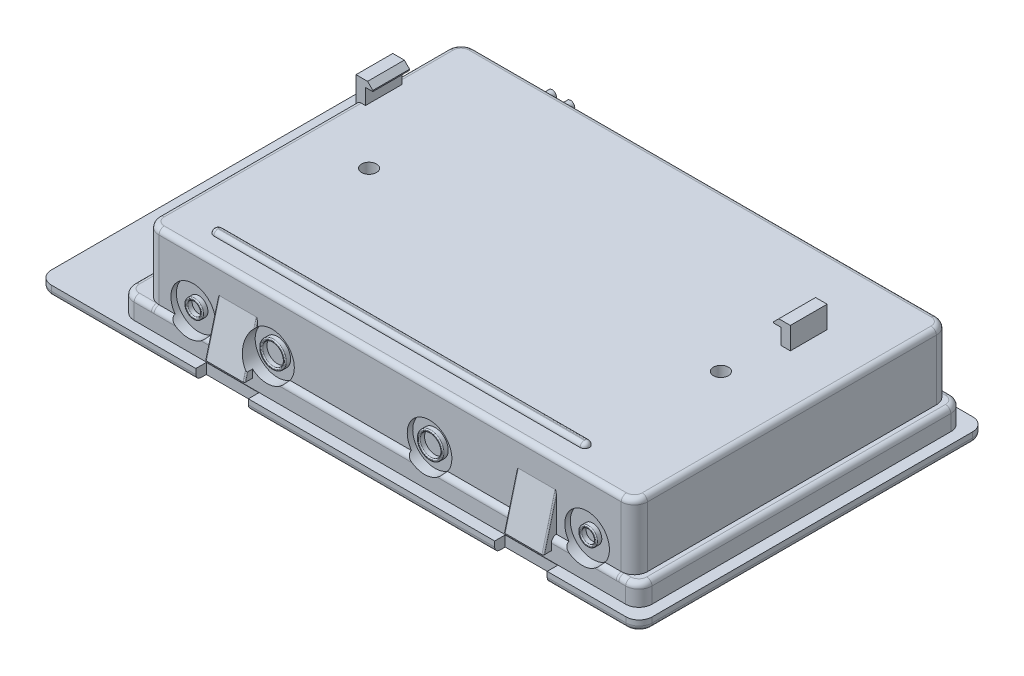
SolidWorks part; units mm, degrees
ref_plane "Front Plane" through (0, 0, 0) normal (0, 0, 1) x (1, 0, 0)
ref_plane "Top Plane" through (0, 0, 0) normal (0, 1, 0) x (1, 0, 0)
ref_plane "Right Plane" through (0, 0, 0) normal (1, 0, 0) x (0, 0, -1)
sketch "Sketch1" plane through (0, 0, 0) normal (0, 1, 0) x (1, 0, 0)
  line L0 (-21.0657, 0) -> (0, 0) construction
  line L1 (0, 0) -> (0, 20.0058) construction
  line L3 (-57.2, 33) -> (57.2, 33)
  line L4 (-57.2, 33) -> (-57.2, -33)
  line L5 (-57.2, -33) -> (57.2, -33)
  line L6 (57.2, 33) -> (57.2, -33)
  dimension "D1" = 114.4
  dimension "D2" = 66
extrude "Boss-Extrude1" add sketch "Sketch1" along normal blind 2
sketch "Sketch2" plane through (0, 2, 0) normal (0, 1, 0) x (1, 0, 0)
  line L0 (0, 0) -> (18.8821, 0) construction
  line L1 (-43.5, 30.95) -> (55.1, 30.95)
  line L2 (-43.5, 30.95) -> (-43.5, -30.95)
  line L3 (-43.5, -30.95) -> (55.1, -30.95)
  line L4 (55.1, 30.95) -> (55.1, -30.95)
  line L5 (57.2, -33) -> (57.2, 33) construction
  dimension "D1" = 98.6
  dimension "D2" = 61.9
  dimension "D3" = 2.1
extrude "Boss-Extrude2" add sketch "Sketch2" along normal blind 4
sketch "Sketch3" plane through (0, 6, 0) normal (0, 1, 0) x (1, 0, 0)
  line L0 (0, 0) -> (11.2165, 0) construction
  line L1 (55.1, -30.95) -> (55.1, 30.95) construction
  line L2 (-39.7, 30) -> (53.3, 30)
  line L3 (-39.7, 30) -> (-39.7, -30)
  line L4 (-39.7, -30) -> (53.3, -30)
  line L5 (53.3, 30) -> (53.3, -30)
  dimension "D1" = 60
  dimension "D2" = 93
  dimension "D3" = 1.8
extrude "Boss-Extrude3" add sketch "Sketch3" along normal blind 12.5
fillet "Fillet1" radius 2.5 12 edges at (-57.2, 1, -33) (-43.5, 4, -30.95) (57.2, 1, -33) (55.1, 4, -30.95) (57.2, 1, 33) (55.1, 4, 30.95) (-57.2, 1, 33) (-43.5, 4, 30.95) (53.3, 12.25, 30) (-39.7, 12.25, 30) (-39.7, 12.25, -30) (53.3, 12.25, -30)
sketch "Sketch4" plane through (0, 18.5, 0) normal (0, 1, 0) x (1, 0, 0)
  line L0 (-39.7, 27.5) -> (-39.7, -27.5) construction
  line L1 (-39.7, 17) -> (-36.5, 17)
  line L2 (-39.7, 17) -> (-39.7, 10)
  line L3 (-39.7, 10) -> (-36.5, 10)
  line L4 (-36.5, 17) -> (-36.5, 10)
  line L5 (50.8, 30) -> (-37.2, 30) construction
  dimension "D1" = 13
  dimension "D2" = 7
  dimension "D3" = 3.2
extrude "Boss-Extrude4" add sketch "Sketch4" along normal blind 4.2
pattern_linear "LPattern1" count 2 spacing 79.5 along (1, 0, 0) of "Boss-Extrude4"
fillet "Fillet2" radius 1 24 edges at (-42.7678, 6, 30.2178) (-43.5, 6, 0) (-42.7678, 6, -30.2178) (5.8, 6, -30.95) (54.3678, 6, -30.2178) (55.1, 6, 0) (54.3678, 6, 30.2178) (-38.9678, 18.5, 29.2678) (-38.9678, 18.5, -29.2678) (6.8, 18.5, -30) (52.5678, 18.5, -29.2678) (53.3, 18.5, 0) (52.5678, 18.5, 29.2678) (56.4678, 0, -32.2678) (57.2, 0, 0) (56.4678, 0, 32.2678) (0, 0, 33) (-56.4678, 0, 32.2678) (-57.2, 0, 0) (-56.4678, 0, -32.2678) (5.8, 6, 30.95) (6.8, 18.5, 30) (0, 0, -33)
chamfer "Chamfer1" distance 1 angle 45 2 edges at (39.8, 22.7, -13.5) (-36.5, 22.7, -13.5)
sketch "Sketch7" plane through (0, 0, -10) normal (0, 0, 1) x (1, 0, 0)
  line L0 (-39.7, 22.7) -> (-39.7, 17.5) construction
  line L1 (-36.5, 18.5) -> (-37.9, 18.5)
  line L2 (-36.5, 18.5) -> (-36.5, 21.5)
  line L3 (-36.5, 21.5) -> (-37.9, 21.5)
  line L4 (-37.9, 18.5) -> (-37.9, 21.5)
  line L5 (39.8, 18.5) -> (41.2, 18.5)
  line L6 (39.8, 18.5) -> (39.8, 21.5)
  line L7 (39.8, 21.5) -> (41.2, 21.5)
  line L8 (41.2, 18.5) -> (41.2, 21.5)
  dimension "D1" = 3
  dimension "D2" = 1.8
extrude "Cut-Extrude1" cut sketch "Sketch7" against normal through all
sketch "Sketch6" plane through (0, 0, 0) normal (0, -1, 0) x (-1, 0, 0)
  line L0 (0, 0) -> (-21.3167, 0) construction
  line L4 (57.2, 30.5) -> (57.2, -30.5) construction
  line L7 (0, 0) -> (0, -39.8642) construction
  line L8 (46.95, 7.6) -> (41.2, 7.6)
  line L9 (46.95, -7.6) -> (41.2, -7.6)
  line L10 (41.2, -7.6) -> (41.2, 7.6)
  line L11 (46.95, 7.6) -> (41.2, 7.6)
  line L12 (46.95, -7.6) -> (41.2, -7.6)
  arc A1 (46.95, 7.6) -> (46.95, -7.6) centre (65.4497, 0) ccw
  dimension "D3" = 16
  dimension "D1" = 20
  dimension "D2" = 15.2
  dimension "D4" = 5.75
extrude "Boss-Extrude5" add sketch "Sketch6" along normal blind 1.25 contours A1 L8 L10 L9 region at (-43.5919, 0, 0)
fillet "Fillet3" radius 1 2 edges at (-46.95, -0.625, 7.6) (-46.95, -0.625, -7.6)
sketch "Sketch9" plane through (0, 0, 0) normal (0, -1, 0) x (1, 0, 0)
  line L1 (-38.6, 12.25) -> (-51.6, 12.25)
  line L2 (-38.6, 12.25) -> (-38.6, -12.25)
  line L3 (-38.6, -12.25) -> (-51.6, -12.25)
  line L4 (-51.6, 12.25) -> (-51.6, -12.25)
  line L5 (0, 0) -> (18.3274, 0) construction
  line L9 (-57.2, -30.5) -> (-57.2, 30.5) construction
  dimension "D1" = 5.6
  dimension "D2" = 13
  dimension "D3" = 24.5
extrude "Cut-Extrude2" cut sketch "Sketch9" against normal blind 1
fillet "Fillet4" radius 0.75 2 edges at (-51.6, 0.5, 12.25) (-51.6, 0.5, -12.25)
fillet "Fillet5" radius 2 2 edges at (-38.6, 0.5, -12.25) (-38.6, 0.5, 12.25)
sketch "Sketch10" plane through (0, 0, 0) normal (0, -1, 0) x (1, 0, 0)
  line L1 (-27.2, 31) -> (-17.2, 31)
  line L2 (-27.2, 31) -> (-27.2, 33)
  line L3 (-27.2, 33) -> (-17.2, 33)
  line L4 (-17.2, 31) -> (-17.2, 33)
  line L6 (39.7, 31) -> (29.7, 31)
  line L7 (39.7, 31) -> (39.7, 33)
  line L8 (39.7, 33) -> (29.7, 33)
  line L9 (29.7, 31) -> (29.7, 33)
  line L10 (-57.2, -30.5) -> (-57.2, 30.5) construction
  line L11 (-54.7, 33) -> (54.7, 33) construction
  point P10 (29.7, 32)
  dimension "D1" = 10
  dimension "D2" = 2
  dimension "D3" = 56.9
  dimension "D4" = 30
extrude "Cut-Extrude3" cut sketch "Sketch10" against normal through all
ref_plane "Plane1" through (-25.95, 0, 0) normal (1, 0, 0) x (0, 0, -1)
sketch "Sketch13" plane through (-25.95, 0, 0) normal (1, 0, 0) x (0, 0, -1)
  line L0 (-32.5, 3.75) -> (-30, 13.25)
  line L1 (-30, 6) -> (-30, 17.5) construction
  line L2 (-30, 13.25) -> (-30, 3.75)
  line L3 (-30, 3.75) -> (-32.5, 3.75)
  line L4 (30.5, 0) -> (-30.5, 0) construction
  line L5 (-33, 1) -> (-33, 2) construction
  dimension "D1" = 3.75
  dimension "D2" = 0.5
  dimension "D3" = 9.5
extrude "Boss-Extrude7" add sketch "Sketch13" along normal blind 7.5 contours L0 L2 L3
fillet "Fillet12" radius 0.25 2 edges at (-25.95, 8.5, 31.25) (-18.45, 8.5, 31.25)
pattern_linear "LPattern2" count 2 spacing 56.9 along (1, 0, 0) of "Boss-Extrude7", "Fillet12"
sketch "Sketch14" plane through (0, 0, -30) normal (0, 0, -1) x (-1, 0, 0)
  line L0 (-54.7, 2) -> (54.7, 2) construction
  line L1 (-31.2, 2) -> (-33.9, 2)
  line L2 (-31.2, 2) -> (-31.2, 7.65)
  line L3 (-31.2, 7.65) -> (-33.9, 7.65)
  line L4 (-33.9, 2) -> (-33.9, 7.65)
  line L5 (-57.2, 1) -> (-57.2, 2) construction
  line L6 (19.25, 2) -> (16.55, 2)
  line L7 (19.25, 2) -> (19.25, 7.65)
  line L8 (19.25, 7.65) -> (16.55, 7.65)
  line L9 (16.55, 2) -> (16.55, 7.65)
  point P12 (-57.2, 1.5)
  dimension "D1" = 26
  dimension "D2" = 47.75
  dimension "D3" = 2.7
  dimension "D4" = 5.65
extrude "Boss-Extrude8" add sketch "Sketch14" along normal blind 2
sketch "Sketch11" plane through (0, 0, 30.95) normal (0, 0, 1) x (1, 0, 0)
  line L0 (-37.2, 18.5) -> (50.8, 18.5) construction
  line L1 (-39.7, 6) -> (-39.7, 17.5) construction
  line L2 (53.3, 17.5) -> (53.3, 6) construction
  circle A0 centre (-30.7, 8.5) radius 4.25
  circle A1 centre (-15.7, 8.5) radius 4.25
  circle A2 centre (14.3, 8.5) radius 4.25
  circle A3 centre (44.3, 8.5) radius 4.25
  point P10 (-39.7, 11.75)
  dimension "D1" = 8.5
  dimension "D2" = 10
  dimension "D3" = 9
  dimension "D4" = 15
  dimension "D5" = 9
  dimension "D6" = 30
extrude "Cut-Extrude4" cut sketch "Sketch11" against normal blind 2 and the other way through all
sketch "Sketch12" plane through (0, 0, 28.95) normal (0, 0, 1) x (1, 0, 0)
  circle A0 centre (-30.7, 8.5) radius 1.75
  circle A1 centre (-30.7, 8.5) radius 1.25
  circle A2 centre (-15.7, 8.5) radius 2.5
  circle A3 centre (-15.7, 8.5) radius 2
  circle A4 centre (14.3, 8.5) radius 2.5
  circle A5 centre (14.3, 8.5) radius 2
  circle A6 centre (44.3, 8.5) radius 1.75
  circle A7 centre (44.3, 8.5) radius 1.25
  dimension "D1" = 3.5
  dimension "D2" = 0.5
  dimension "D3" = 5
  dimension "D4" = 0.5
extrude "Boss-Extrude6" add sketch "Sketch12" along normal blind 1
sketch "Sketch15" plane through (0, 18.5, 0) normal (0, 1, 0) x (1, 0, 0)
  line L0 (53.3, 27.5) -> (53.3, -27.5) construction
  line L1 (-31.7, -24.2) -> (39.8, -24.2)
  line L2 (-31.7, -24.2) -> (-31.7, -25.95)
  line L3 (-31.7, -25.95) -> (39.8, -25.95)
  line L4 (39.8, -24.2) -> (39.8, -25.95)
  line L5 (-39.7, -27.5) -> (-39.7, 10) construction
  line L6 (-31.95, -29.95) -> (-29.45, -29.95) construction
  dimension "D1" = 1.75
  dimension "D2" = 13.5
  dimension "D3" = 8
  dimension "D4" = 4
extrude "Boss-Extrude9" add sketch "Sketch15" along normal blind 0.8
fillet "Fillet8" 2 edges at (-31.7, 18.9, 24.2) (-31.7, 18.9, 25.95) type full round first side face at (4.05, 18.9, 24.2) second side face at (4.05, 18.9, 25.95) middle face at (-31.7, 18.9, 25.075)
fillet "Fillet9" 2 edges at (39.8, 18.9, 25.95) (39.8, 18.9, 24.2) type full round first side face at (4.4875, 18.9, 25.95) second side face at (4.4875, 18.9, 24.2) middle face at (39.8, 18.9, 25.075)
fillet "Fillet10" radius 0.8 4 edges at (-31.7, 19.3, 25.075) (4.05, 19.3, 24.2) (39.8, 19.3, 25.075) (4.05, 19.3, 25.95)
sketch "Sketch16" plane through (0, 0, -30) normal (0, 0, -1) x (-1, 0, 0)
  circle A0 centre (15.7, 8.5) radius 4.25 construction
  circle A1 centre (15.7, 8.5) radius 4.25
  circle A2 centre (30.7, 8.5) radius 4.25 construction
  circle A3 centre (30.7, 8.5) radius 4.25
  circle A4 centre (0.7, 8.5) radius 4.25
  circle A5 centre (-29.3, 8.5) radius 4.25
  dimension "D1" = 15
  dimension "D2" = 30
extrude "Cut-Extrude5" cut sketch "Sketch16" against normal blind 2 and the other way through all
ref_plane "Plane2" through (39.7, 0, 31) normal (1, 0, 0) x (0, 0, -1)
sketch "Sketch18" plane through (0, 0, -28) normal (0, 0, -1) x (-1, 0, 0)
  circle A0 centre (-29.3, 8.5) radius 2
  circle A1 centre (-29.3, 8.5) radius 2.5
  circle A2 centre (0.7, 8.5) radius 2
  circle A3 centre (0.7, 8.5) radius 2.5
  circle A4 centre (15.7, 8.5) radius 1.25
  circle A5 centre (15.7, 8.5) radius 1.75
  circle A6 centre (30.7, 8.5) radius 1.25 construction
  circle A7 centre (30.7, 8.5) radius 1.75 construction
  circle A8 centre (30.7, 8.5) radius 1.25
  circle A9 centre (30.7, 8.5) radius 1.75
  dimension "D1" = 5
  dimension "D2" = 0.5
extrude "Boss-Extrude10" add sketch "Sketch18" along normal blind 1
fillet "Fillet11" radius 0.2 16 edges at (-31.95, 8.5, -29) (-32.45, 8.5, -29) (-16.95, 8.5, -29) (-17.45, 8.5, -29) (-2.7, 8.5, -29) (-3.2, 8.5, -29) (27.3, 8.5, -29) (26.8, 8.5, -29) (45.55, 8.5, 29.95) (46.05, 8.5, 29.95) (16.3, 8.5, 29.95) (16.8, 8.5, 29.95) (-13.7, 8.5, 29.95) (-13.2, 8.5, 29.95) (-29.45, 8.5, 29.95) (-28.95, 8.5, 29.95)
sketch "Sketch19" plane through (0, 0, -30) normal (0, 0, -1) x (-1, 0, 0)
  line L0 (-50.8, 18.5) -> (37.2, 18.5) construction
  line L1 (15.7, 8.5) -> (30.7, 8.5) construction
  line L2 (23.2, 8.5) -> (23.2, 25.6788) construction
  circle A0 centre (21.45, 15.5) radius 0.8
  circle A1 centre (24.95, 15.5) radius 0.8
  dimension "D1" = 1.6
  dimension "D2" = 3.5
  dimension "D3" = 3
extrude "Boss-Extrude11" add sketch "Sketch19" along normal blind 2.6
sketch "Sketch20" plane through (0, 18.5, 0) normal (0, 1, 0) x (1, 0, 0)
  line L0 (41.2, 11.1705) -> (41.2, -5.7372) construction
  line L1 (41.2, 17) -> (41.2, 10) construction
  circle A0 centre (-27.225, 0) radius 1.425
  circle A1 centre (39.775, 0) radius 1.425
  dimension "D1" = 2.85
  dimension "D2" = 67
extrude "Cut-Extrude6" cut sketch "Sketch20" against normal blind 16.4
sketch "Sketch21" plane through (0, 0, 0) normal (0, -1, 0) x (1, 0, 0)
  line L0 (-38.6, -10.25) -> (-38.6, 10.25) construction
  line L1 (-23.6, 12.25) -> (-8.6, 12.25)
  line L2 (-23.6, 12.25) -> (-23.6, -12.25)
  line L3 (-23.6, -12.25) -> (-8.6, -12.25)
  line L4 (-8.6, 12.25) -> (-8.6, -12.25)
  line L5 (-50.85, -12.25) -> (-40.6, -12.25) construction
  line L6 (-40.6, 12.25) -> (-50.85, 12.25) construction
  dimension "D1" = 15
  dimension "D2" = 15
extrude "Cut-Extrude7" cut sketch "Sketch21" against normal blind 0.5
fillet "Fillet13" radius 0.25 4 edges at (-23.6, 0.25, -12.25) (-8.6, 0.25, -12.25) (-8.6, 0.25, 12.25) (-23.6, 0.25, 12.25)
fillet "Fillet14" radius 0.25 8 edges at (-23.5268, 0.5, 12.1768) (-16.1, 0.5, 12.25) (-8.6732, 0.5, 12.1768) (-8.6, 0.5, 0) (-8.6732, 0.5, -12.1768) (-16.1, 0.5, -12.25) (-23.5268, 0.5, -12.1768) (-23.6, 0.5, 0)
sketch "Sketch22" plane through (0, 0.5, 0) normal (0, -1, 0) x (1, 0, 0)
  line L0 (-15.7529, -9.4649) -> (-15.7529, 8.4831) construction
  text T0 "DC9V" font "Calibri" height 5.3
extrude "Boss-Extrude12" add sketch "Sketch22" along normal blind 0.5
sketch "Sketch25" plane through (0, 0, 0) normal (0, 0, 1) x (1, 0, 0)
  line L0 (-41.3, 6) -> (-39.7, 12)
  line L1 (-41, 6) -> (-42.5, 6) construction
  line L2 (-39.7, 6) -> (-39.7, 17.5) construction
  line L3 (-41, 6) -> (-37.6975, 6) construction
  dimension "D1" = 6
  dimension "D2" = 1.6
rib "Rib1" sketch "Sketch25" sketch "Sketch25" thickness 20.5 extrusion direction parallel to sketch draft on no parameters "D1"=20.5
